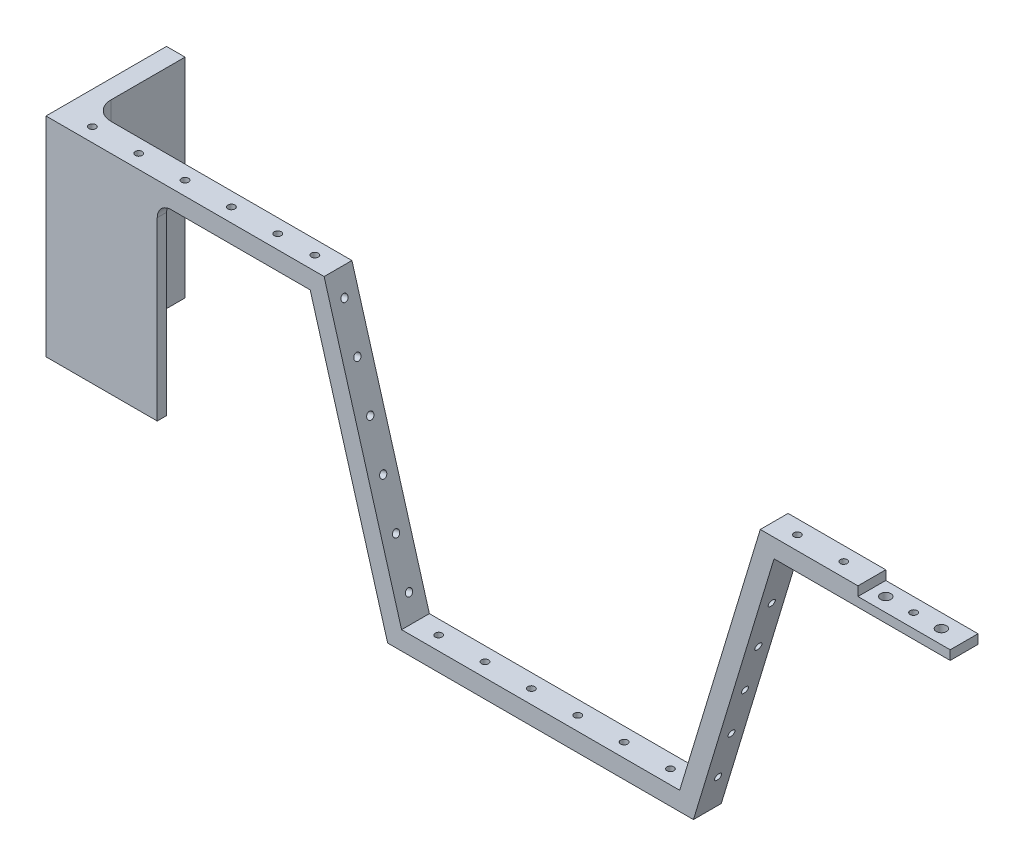
SolidWorks part; units mm, degrees
ref_plane "Front Plane" through (0, 0, 0) normal (0, 0, 1) x (1, 0, 0)
ref_plane "Top Plane" through (0, 0, 0) normal (0, 1, 0) x (1, 0, 0)
ref_plane "Right Plane" through (0, 0, 0) normal (1, 0, 0) x (0, 0, -1)
sketch "Sketch1" plane through (0, 0, 0) normal (0, 0, 1) x (1, 0, 0)
  line L0 (-23.7058, 144.923) -> (-23.7058, 142.923)
  line L1 (-23.6058, 144.923) -> (-43.6058, 144.923) construction
  line L2 (-23.7058, 142.923) -> (-61.7058, 142.923)
  line L3 (-61.7058, 142.923) -> (-79.0939, 85.4978)
  line L4 (-79.0939, 85.4978) -> (-145.0669, 85.4978)
  line L5 (-145.0669, 85.4978) -> (-161.7783, 143.1235)
  line L6 (-161.7783, 143.1235) -> (-214.7735, 143.1235)
  line L7 (-214.7735, 143.1235) -> (-214.7735, 102.1235)
  line L8 (-214.7735, 102.1235) -> (-218.7735, 102.1235)
  line L9 (-218.7735, 102.1235) -> (-218.7735, 147.1235)
  line L10 (-218.7735, 147.1235) -> (-158.7735, 147.1235)
  line L11 (-158.7735, 147.1235) -> (-142.0621, 89.4978)
  line L12 (-142.0621, 89.4978) -> (-82.0621, 89.4978)
  line L13 (-82.0621, 89.4978) -> (-64.674, 146.923)
  line L14 (-64.674, 146.923) -> (-43.6058, 146.923)
  line L15 (-43.6058, 146.923) -> (-43.6058, 144.923)
  line L16 (-43.6058, 144.923) -> (-23.7058, 144.923)
  dimension "D1" = 38
  dimension "D2" = 60
  dimension "D3" = 60
  dimension "D4" = 60
  dimension "D5" = 60
  dimension "D6" = 2
  dimension "D7" = 2
  dimension "D8" = 4
  dimension "D9" = 4
  dimension "D10" = 4
  dimension "D11" = 4
  dimension "D12" = 4
  dimension "D13" = 45
  dimension "D14" = 19.9
extrude "Boss-Extrude1" add sketch "Sketch1" along normal blind 6
sketch "Sketch2" plane through (0, 144.923, 0) normal (0, 1, 0) x (1, 0, 0)
  line L0 (-23.7058, -6) -> (-23.7058, 0) construction
  line L1 (-23.7058, -6) -> (-43.6058, -6) construction
  circle A0 centre (-28.6058, -3) radius 1.1
  circle A1 centre (-40.6058, -3) radius 1.1
  dimension "D1" = 2.2
  dimension "D2" = 2.2
  dimension "D3" = 4.9
  dimension "D4" = 3
  dimension "D5" = 3
  dimension "D6" = 16.9
extrude "Cut-Extrude1" cut sketch "Sketch2" against normal blind 6
sketch "Sketch3" plane through (0, 144.923, 0) normal (0, 1, 0) x (1, 0, 0)
  circle A0 centre (-34.6058, -3) radius 0.75
extrude "Cut-Extrude2" cut sketch "Sketch3" against normal blind 6
sketch "Sketch4" plane through (0, 146.923, 0) normal (0, 1, 0) x (1, 0, 0)
  line L0 (-43.6058, -6) -> (-64.674, -6) construction
  line L1 (-64.674, -6) -> (-64.674, 0) construction
  circle A0 centre (-59.674, -3) radius 0.75
  circle A1 centre (-49.674, -3) radius 0.75
  dimension "D1" = 1.5
  dimension "D2" = 3
  dimension "D3" = 5
  dimension "D4" = 1.5
  dimension "D5" = 3
  dimension "D6" = 15
extrude "Cut-Extrude3" cut sketch "Sketch4" against normal blind 6
sketch "Sketch5" plane through (-99.9937, 30.2776, 0) normal (-0.9571, 0.2898, 0) x (0, 0, 1)
  line L0 (6, 121.8754) -> (6, 61.8754) construction
  line L1 (6, 121.8754) -> (0, 121.8754) construction
  circle A0 centre (3, 116.8754) radius 0.75
  circle A1 centre (3, 106.8754) radius 0.75
  circle A2 centre (3, 96.8754) radius 0.75
  circle A3 centre (3, 86.8754) radius 0.75
  circle A4 centre (3, 76.8754) radius 0.75
  circle A5 centre (3, 66.8754) radius 0.75
  dimension "D1" = 1.5
  dimension "D2" = 3
  dimension "D3" = 5
  dimension "D4" = 6
extrude "Cut-Extrude4" cut sketch "Sketch5" against normal blind 6
sketch "Sketch6" plane through (0, 89.4978, 0) normal (0, 1, 0) x (1, 0, 0)
  line L0 (-82.0621, -6) -> (-142.0621, -6) construction
  line L1 (-82.0621, -6) -> (-82.0621, 0) construction
  circle A0 centre (-87.0621, -3) radius 0.75
  circle A1 centre (-97.0621, -3) radius 0.75
  circle A2 centre (-107.0621, -3) radius 0.75
  circle A3 centre (-117.0621, -3) radius 0.75
  circle A4 centre (-127.0621, -3) radius 0.75
  circle A5 centre (-137.0621, -3) radius 0.75
  dimension "D1" = 1.5
  dimension "D2" = 3
  dimension "D3" = 5
  dimension "D4" = 6
extrude "Cut-Extrude5" cut sketch "Sketch6" against normal blind 6
sketch "Sketch7" plane through (-107.1006, -31.0592, 0) normal (0.9604, 0.2785, 0) x (0, 0, -1)
  line L0 (0, 125.524) -> (0, 185.524) construction
  line L1 (-6, 185.524) -> (0, 185.524) construction
  circle A0 centre (-3, 180.524) radius 0.75
  circle A1 centre (-3, 170.524) radius 0.75
  circle A2 centre (-3, 160.524) radius 0.75
  circle A3 centre (-3, 150.524) radius 0.75
  circle A4 centre (-3, 140.524) radius 0.75
  circle A5 centre (-3, 130.524) radius 0.75
  dimension "D1" = 1.5
  dimension "D2" = 3
  dimension "D3" = 5
  dimension "D4" = 6
extrude "Cut-Extrude6" cut sketch "Sketch7" against normal blind 6
sketch "Sketch8" plane through (0, 147.1235, 0) normal (0, 1, 0) x (1, 0, 0)
  line L0 (-158.7735, 0) -> (-218.7735, 0) construction
  line L1 (-218.7735, -6) -> (-218.7735, 0) construction
  circle A0 centre (-211.7735, -3) radius 0.75
  circle A1 centre (-201.7735, -3) radius 0.75
  circle A2 centre (-191.7735, -3) radius 0.75
  circle A3 centre (-181.7735, -3) radius 0.75
  circle A4 centre (-171.7735, -3) radius 0.75
  dimension "D1" = 1.5
  dimension "D2" = 3
  dimension "D3" = 7
  dimension "D4" = 5
extrude "Cut-Extrude7" cut sketch "Sketch8" against normal blind 6
sketch "Sketch9" plane through (0, 147.1235, 0) normal (0, 1, 0) x (1, 0, 0)
  line L0 (-158.7735, -6) -> (-158.7735, 0) construction
  line L1 (-158.7735, -6) -> (-218.7735, -6) construction
  circle A0 centre (-163.7735, -3) radius 0.75
  dimension "D1" = 1.5
  dimension "D2" = 5
  dimension "D3" = 3
extrude "Cut-Extrude8" cut sketch "Sketch9" against normal blind 6
sketch "Sketch10" plane through (-218.7735, 0, 0) normal (-1, 0, 0) x (0, 0, 1)
  line L1 (0, 147.1235) -> (-20, 147.1235)
  line L2 (0, 147.1235) -> (0, 102.1235)
  line L3 (0, 102.1235) -> (-20, 102.1235)
  line L4 (-20, 147.1235) -> (-20, 102.1235)
extrude "Boss-Extrude2" add sketch "Sketch10" against normal blind 4
fillet "Fillet1" radius 4 2 edges at (-214.7735, 143.1235, 3) (-214.7735, 145.1235, 0)
sketch "Sketch11" plane through (0, 143.1235, 0) normal (0, -1, 0) x (1, 0, 0)
  line L1 (-214.7735, 6) -> (-194.7735, 6)
  line L2 (-214.7735, 6) -> (-214.7735, 4)
  line L3 (-214.7735, 4) -> (-194.7735, 4)
  line L4 (-194.7735, 6) -> (-194.7735, 4)
  dimension "D1" = 20
  dimension "D2" = 2
extrude "Boss-Extrude3" add sketch "Sketch11" along normal up to surface (41 mm away) up to face at (-216.7735, 102.1235, -7)
fillet "Fillet2" radius 3 3 edges at (-214.7735, 120.6235, 4) (-213.602, 141.952, 4) (-202.7735, 143.1235, 4)
fillet "Fillet3" radius 3 1 edges at (-194.7735, 143.1235, 3.5)
sketch "Sketch12" plane through (-214.7735, 0, 0) normal (1, 0, 0) x (0, 0, -1)
  line L0 (20, 147.1235) -> (20, 102.1235) construction
  line L1 (3.1, 111.2084) -> (-1.1, 111.2084)
  line L2 (3.1, 111.2084) -> (3.1, 118.2084)
  line L3 (3.1, 118.2084) -> (-1.1, 118.2084)
  line L4 (-1.1, 111.2084) -> (-1.1, 118.2084)
  line L5 (10.9, 118.5313) -> (15.1, 118.5313)
  line L6 (10.9, 118.5313) -> (10.9, 111.5313)
  line L7 (10.9, 111.5313) -> (15.1, 111.5313)
  line L8 (15.1, 118.5313) -> (15.1, 111.5313)
  line L9 (-6, 85.4978) -> (-6, 142.923) construction
  dimension "D1" = 4.2
  dimension "D2" = 7
  dimension "D3" = 7
  dimension "D4" = 4.2
  dimension "D5" = 4.9
  dimension "D6" = 4.9
extrude "Cut-Extrude9" cut sketch "Sketch12" against normal blind 4
